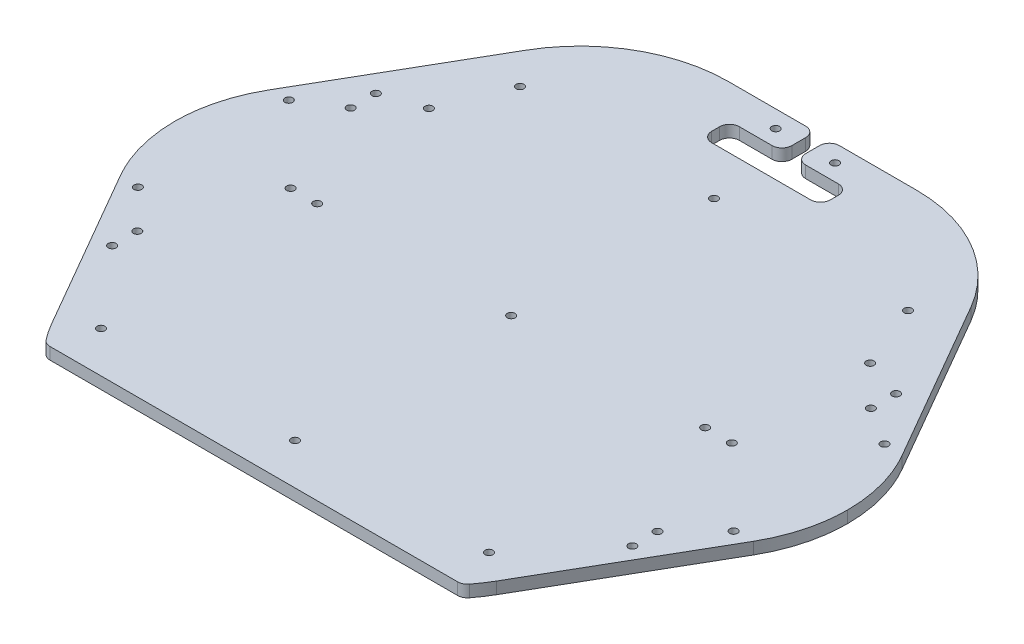
SolidWorks part; units mm, degrees
ref_plane "Front Plane" through (0, 0, 0) normal (0, 0, 1) x (1, 0, 0)
ref_plane "Top Plane" through (0, 0, 0) normal (0, 1, 0) x (1, 0, 0)
ref_plane "Right Plane" through (0, 0, 0) normal (1, 0, 0) x (0, 0, -1)
ref_plane "Plane1" through (0, 6, 0) normal (0, 1, 0) x (1, 0, 0)
sketch "Sketch1" plane through (0, 6, 0) normal (0, 1, 0) x (1, 0, 0)
  line L0 (112.4519, -119.7724) -> (159.9519, -37.5)
  line L1 (159.9519, 37.5) -> (90.8013, 157.2724)
  line L2 (90.8013, 157.2724) -> (-90.8013, 157.2724)
  line L3 (-90.8013, 157.2724) -> (-159.9519, 37.5)
  line L4 (-159.9519, -37.5) -> (-112.4519, -119.7724)
  line L5 (-105.3856, -130) -> (105.3856, -130)
  spline S0 degree 3 poles (105.3856, -130) (105.779, -129.4973) (106.1723, -128.9946) (106.5657, -128.4919) (108.7286, -125.7279) (110.697, -122.8118) (112.4519, -119.7724) knots 2.452075 2.452075 2.452075 2.452075 2.477608 2.477608 2.477608 2.617994 2.617994 2.617994 2.617994
  spline S1 degree 3 poles (159.9519, -37.5) (162.0898, -33.7968) (165.8426, -25.7861) (169.2445, -13.0899) (169.9999, -4.2761) (170, 0) knots 2.617994 2.617994 2.617994 2.617994 2.789036 2.97055 3.141593 3.141593 3.141593 3.141593
  spline S2 degree 3 poles (170, 0) (169.9999, 4.276) (169.2445, 13.0899) (165.8426, 25.7861) (162.0898, 33.7968) (159.9519, 37.5) knots 3.141593 3.141593 3.141593 3.141593 3.312635 3.494149 3.665191 3.665191 3.665191 3.665191
  spline S3 degree 3 poles (-159.9519, 37.5) (-162.0898, 33.7968) (-165.8426, 25.7861) (-169.2445, 13.0899) (-169.9999, 4.2761) (-170, 0) knots 5.759587 5.759587 5.759587 5.759587 5.930629 6.112143 6.283185 6.283185 6.283185 6.283185
  spline S4 degree 3 poles (-170, 0) (-169.9999, -4.2761) (-169.2445, -13.0899) (-165.8426, -25.7861) (-162.0898, -33.7968) (-159.9519, -37.5) knots 6.283185 6.283185 6.283185 6.283185 6.454228 6.635742 6.806784 6.806784 6.806784 6.806784
  spline S5 degree 3 poles (-112.4519, -119.7724) (-110.697, -122.8118) (-108.7286, -125.7279) (-106.5657, -128.4919) (-106.1723, -128.9946) (-105.779, -129.4973) (-105.3856, -130) knots 0.523599 0.523599 0.523599 0.523599 0.663985 0.663985 0.663985 0.689517 0.689517 0.689517 0.689517
extrude "Boss-Extrude1" add sketch "Sketch1" against normal blind 6
sketch "Sketch2" plane through (0, 0, 0) normal (0, -1, 0) x (1, 0, 0)
  line L0 (3.5, -157.2724) -> (3.5, -140.2724)
  line L1 (3.5, -140.2724) -> (30, -140.2724)
  line L2 (30, -140.2724) -> (30, -126.2724)
  line L3 (30, -126.2724) -> (-30, -126.2724)
  line L4 (-30, -126.2724) -> (-30, -140.2724)
  line L5 (-30, -140.2724) -> (-3.5, -140.2724)
  line L6 (-3.5, -140.2724) -> (-3.5, -157.2724)
  line L7 (-3.5, -157.2724) -> (3.5, -157.2724)
extrude "Cut-Extrude1" cut sketch "Sketch2" against normal through all
hole_wizard "M3.5 Clearance Hole1" positions "Sketch4" profile "Sketch3" hole size "M3.5" standard "ANSI Metric"
sketch "Sketch4" plane through (0, 0, 0) normal (0, -1, 0) x (-1, 0, 0)
  point P0 (98, -109.22)
  point P1 (-98, 102.4382)
  point P2 (98, 102.4382)
  point P3 (0, 102.4382)
  point P4 (0, -109.22)
  point P5 (0, 0)
  point P6 (-97.9932, 0)
  point P7 (97.9932, 0)
  point P8 (111.4552, 69.85)
  point P9 (111.4552, 0)
  point P10 (-111.4552, 69.85)
  point P11 (-111.4552, 0)
  point P12 (-98, -109.22)
  point P13 (131.4, 50.3)
  point P14 (-131.4, 50.3)
  point P15 (131.4, -70.2)
  point P16 (-131.4, -70.2)
  point P17 (131.4, 63)
  point P18 (-131.4, 63)
  point P19 (131.4, -57.5)
  point P20 (-131.4, -57.5)
  point P21 (15, 148.6)
  point P22 (-15, 148.6)
  point P23 (150.47, 38.1)
  point P24 (150.47, -38.1)
  point P25 (-150.47, 38.1)
  point P26 (-150.47, -38.1)
sketch "Sketch3" plane through (-98, 0, 109.22) normal (1, 0, 0) x (0, 0, -1)
  line L0 (0, 0) -> (0, 6.0001)
  line L1 (0, 6.0001) -> (1.9748, 6.0001)
  line L2 (1.9748, 6.0001) -> (1.9748, 0)
  line L5 (1.9748, 0) -> (0, 0)
  line L11 (0, -6.35) -> (0, 107.95) construction
  dimension "Thru Hole Dia." = 3.9496
  dimension "Thru Hole Depth" = 6.0001
fillet "Fillet1" radius 5.0207 10 edges at (-105.3856, 3, 130) (3.5, 3, -140.2724) (-30, 3, -126.2724) (-30, 3, -140.2724) (-3.5, 3, -140.2724) (30, 3, -140.2724) (105.3856, 3, 130) (30, 3, -126.2724) tangent propagation no
fillet "Fillet2" radius 74.9585 2 edges at (90.8013, 3, -157.2724) (-90.8013, 3, -157.2724) tangent propagation no
